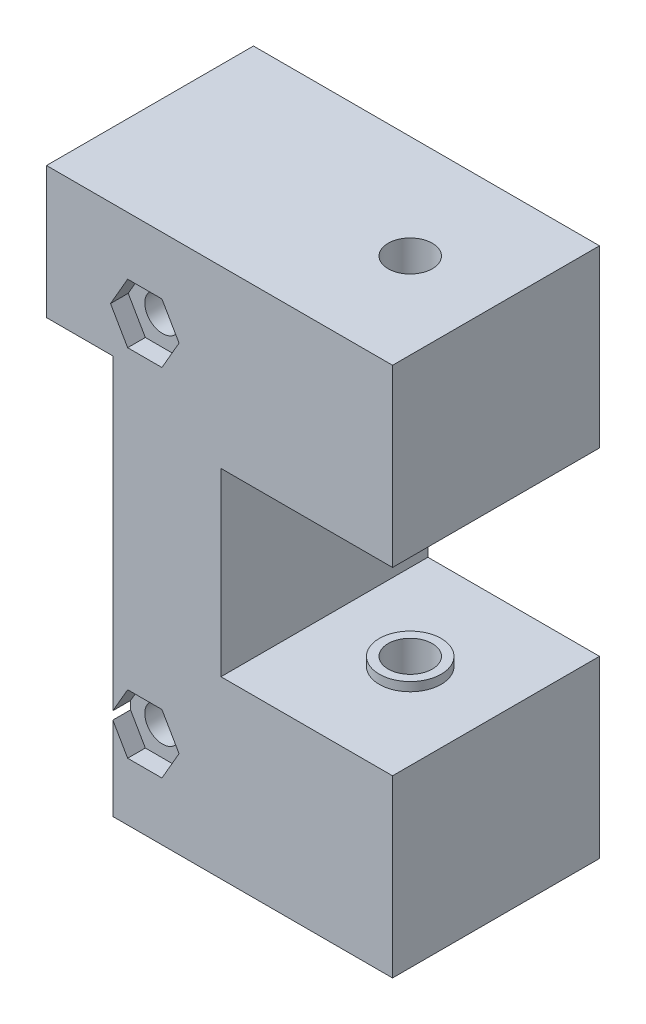
SolidWorks part; units mm, degrees
ref_plane "Front Plane" through (0, 0, 0) normal (0, 0, 1) x (1, 0, 0)
ref_plane "Top Plane" through (0, 0, 0) normal (0, 1, 0) x (1, 0, 0)
ref_plane "Right Plane" through (0, 0, 0) normal (1, 0, 0) x (0, 0, -1)
sketch "MainBlock" plane through (0, 0, 0) normal (0, 0, 1) x (1, 0, 0)
  line L0 (0, 0) -> (39.125, 0)
  line L1 (39.125, 0) -> (39.125, 19.8)
  line L2 (39.125, 19.8) -> (19.725, 19.8)
  line L3 (19.725, 19.8) -> (19.725, 40.2)
  line L4 (19.725, 40.2) -> (39.125, 40.2)
  line L5 (39.125, 40.2) -> (39.125, 60)
  line L6 (39.125, 60) -> (0, 60)
  line L7 (0, 60) -> (0, 0)
  circle A0 centre (11.1125, 50.1) radius 2
  circle A1 centre (11.1125, 9.9) radius 2
  dimension "D4" = 4
  dimension "D1" = 39.125
  dimension "D2" = 60
  dimension "D3" = 20.4
  dimension "D5" = 19.4
  dimension "D6" = 11.1125
  dimension "D7" = 9.9
  dimension "D8" = 9.9
  dimension "D9" = 19.8
  dimension "D10" = 19.8
extrude "MainBlockBoss-Extrude1" add sketch "MainBlock" along normal blind 23.4
sketch "TopHoleCut-Sketch2" plane through (0, 60, 0) normal (0, 1, 0) x (1, 0, 0)
  line L0 (39.125, 0) -> (0, 0) construction
  circle A0 centre (29.425, -11.7) radius 2.5
  dimension "D3" = 5
  dimension "D1" = 11.7
  dimension "D2" = 9.7
extrude "TopHoleCut-Extrude1" cut sketch "TopHoleCut-Sketch2" against normal blind 45
sketch "MountHoleBoreSketch3" plane through (0, 0, 23.4) normal (0, 0, 1) x (1, 0, 0)
  line L1 (14.9875, 50.1) -> (13.05, 53.4558)
  line L2 (13.05, 53.4558) -> (9.175, 53.4558)
  line L3 (9.175, 53.4558) -> (7.2375, 50.1)
  line L4 (7.2375, 50.1) -> (9.175, 46.7442)
  line L5 (9.175, 46.7442) -> (13.05, 46.7442)
  line L6 (13.05, 46.7442) -> (14.9875, 50.1)
  line L7 (14.9875, 9.9) -> (13.05, 13.2558)
  line L8 (13.05, 13.2558) -> (9.175, 13.2558)
  line L9 (9.175, 13.2558) -> (7.2375, 9.9)
  line L10 (7.2375, 9.9) -> (9.175, 6.5442)
  line L11 (9.175, 6.5442) -> (13.05, 6.5442)
  line L12 (13.05, 6.5442) -> (14.9875, 9.9)
  circle A0 centre (11.1125, 50.1) radius 3.3558 construction
  circle A1 centre (11.1125, 9.9) radius 3.3558 construction
  point P10 (11.1125, 53.4558)
  dimension "D1" = 7.75
extrude "MountHoleBoreCut-Extrude2" cut sketch "MountHoleBoreSketch3" against normal blind 2
sketch "TopSpacerSketch4" plane through (0, 40.2, 0) normal (0, -1, 0) x (1, 0, 0)
  circle A0 centre (29.425, 11.7) radius 3.5
  circle A1 centre (29.425, 11.7) radius 2.5
  circle A2 centre (29.425, 11.7) radius 2.5 construction
  dimension "D1" = 7
extrude "TopSpacerBoss-Extrude2" add sketch "TopSpacerSketch4" along normal blind 1
sketch "LowerSpacerSketch5" plane through (0, 19.8, 0) normal (0, 1, 0) x (1, 0, 0)
  circle A0 centre (29.425, -11.7) radius 2.5
  circle A1 centre (29.425, -11.7) radius 2.5 construction
  circle A2 centre (29.425, -11.7) radius 3.5
  circle A3 centre (29.425, -11.7) radius 3.5 construction
extrude "LowerSpacerBoss-Extrude3" add sketch "LowerSpacerSketch5" along normal blind 1
sketch "PushPinHoleSketch1" plane through (0, 0, 0) normal (0, -1, 0) x (1, 0, 0)
  circle A0 centre (29.425, 11.7) radius 1
  circle A1 centre (29.425, 11.7) radius 2.5 construction
  dimension "D1" = 2
extrude "PushPinHoleCut-Extrude1" cut sketch "PushPinHoleSketch1" against normal through all
sketch "MidRailIndentSketch1" plane through (0, 0, 23.4) normal (0, 0, 1) x (1, 0, 0)
  line L0 (0, 60) -> (0, 0) construction
  line L1 (0, 45.1) -> (7.5, 45.1)
  line L2 (0, 45.1) -> (0, 0)
  line L3 (0, 0) -> (7.5, 0)
  line L4 (7.5, 45.1) -> (7.5, 0)
  line L5 (39.125, 60) -> (0, 60) construction
  line L6 (0, 0) -> (39.125, 0) construction
  dimension "D1" = 14.9
  dimension "D3" = 7.5
extrude "MidRailIndentCut-Extrude1" cut sketch "MidRailIndentSketch1" against normal through all
equation "\"BeltTensionerWidth\"= \"MidRailToAlignWithGantryBlock\" + \"BeltTensionerInnerWidth\" / 2 + \"RailThickness\""
equation "\"BeltTensionerHeight\"= 60mm"
equation "\"BeltTensionerDepth\"= \"BeltTensionerBackWallThickness\" + \"BeltTensionerInnerDepth\"'Equals 23.4"
equation "\"BeltTensionerInnerWidth\"= \"20TGT2PulleyDiameter\" + \"BeltTensionerSpaceBetweenPulleyAndWall\""
equation "\"BeltTensionerInnerHeight\"= \"20TGT2PulleyWidth\" * 2 + \"1mmSpacer\" * 3"
equation "\"BeltTensionerBackWallThickness\"= 4mm"
equation "\"BeltTensionerInnerDepth\"= \"20TGT2PulleyDiameter\" + \"BeltTensionerSpaceBetweenPulleyAndWall\""
equation "\"RailThickness\"= .125in'Spec"
equation "\"HoleOffsetFromEdge\"= \"RailThickness\" * 2.5"
equation "\"LinearGBWithRailDepth\"= 12.75mm'Spec"
equation "\"GABDistanceFromBackToFirstPulley\"= 13.5mm"
equation "\"MidRailToAlignWithGantryBlock\"= \"LinearGBWithRailDepth\" + \"GABDistanceFromBackToFirstPulley\"'All outside cogs must align"
equation "\"20TGT2PulleyDiameter\"= 17.9mm'Spec"
equation "\"BeltTensionerSpaceBetweenPulleyAndWall\"= 1.5mm"
equation "\"BeltTensionerMountingHoleDiameter\"= 4.0mm"
equation "\"BeltTensionerMountingHoleOffsetFromTopOrBottom\"= ( \"BeltTensionerHeight\" - \"BeltTensionerInnerHeight\" ) / 4"
equation "\"20TGT2PulleyWidth\"= 8.7mm'The STL of the Pulley in the diagram is a bit larger"
equation "\"1mmSpacer\"= 1mm"
equation "\"SteelShaft5mmHoleDiameter\"= 5mm"
equation "\"BeltTensionerMountingHoleOuterBoreDepth\"= 2mm"
equation "\"BeltTensionerMountingHoleOuterBoreDiameter\"= 7.75mm"
equation "\"7mmx1mmSpacerDiameter\"= 7mm"
equation "\"7mmx1mmSpacerHeight\"= 1mm"
equation "\"D1@MainBlock\" = \"BeltTensionerWidth\""
equation "\"D4@MainBlock\" = \"BeltTensionerMountingHoleDiameter\""
equation "\"D5@MainBlock\" = \"BeltTensionerInnerWidth\""
equation "\"D6@MainBlock\"=\"HoleOffsetFromEdge\" + \"RailThickness\""
equation "\"D7@MainBlock\"=\"BeltTensionerMountingHoleOffsetFromTopOrBottom\""
equation "\"D8@MainBlock\"=\"BeltTensionerMountingHoleOffsetFromTopOrBottom\""
equation "\"D1@MainBlockBoss-Extrude1\" = \"BeltTensionerDepth\""
equation "\"D1@TopHoleCut-Sketch2\" = \"BeltTensionerDepth\" / 2"
equation "\"D3@TopHoleCut-Sketch2\" = \"SteelShaft5mmHoleDiameter\""
equation "\"D1@MountHoleBoreSketch3\" = \"BeltTensionerMountingHoleOuterBoreDiameter\""
equation "\"D1@MountHoleBoreCut-Extrude2\"=\"BeltTensionerMountingHoleOuterBoreDepth\""
equation "\"D1@TopSpacerSketch4\" = \"7mmx1mmSpacerDiameter\""
equation "\"D1@TopSpacerBoss-Extrude2\" = \"7mmx1mmSpacerHeight\""
equation "\"D1@LowerSpacerBoss-Extrude3\" = \"7mmx1mmSpacerHeight\""
equation "\"SteelPinPushHoleDiameter\"= 2mm"
equation "\"D1@PushPinHoleSketch1\" = \"SteelPinPushHoleDiameter\""
equation "\"BeltTensionerSteelShaftHoleDepthFromTop\"= ( \"SteelShaftLength\" - \"BeltTensionerInnerHeight\" ) / 2 + ( \"BeltTensionerHeight\" - \"BeltTensionerInnerHeight\" ) / 2 + \"BeltTensionerInnerHeight\"'Equals 45"
equation "\"SteelShaftLength\"= 30mm"
equation "\"D1@TopHoleCut-Extrude1\"=\"BeltTensionerSteelShaftHoleDepthFromTop\""
equation "\"D2@TopHoleCut-Sketch2\"=\"BeltTensionerWidth\" -\"MidRailToAlignWithGantryBlock\" - \"RailThickness\""
equation "\"D1@MidRailIndentSketch1\"=\"DistanceAboveMidSideRailToBeltTensioner\""
equation "\"LinearRailWidth\"= 12mm'Spec"
equation "\"MidSideRailVerticalOffset\"= \"LinearRailWidth\" + 3mm'Allows space for RodStabilizer to attach to bottom of MidSideRail"
equation "\"DistanceAboveMidSideRailToBeltTensioner\"= \"VS ToTopOfBeltTensionerAlignedWithYAxisGantryBlockUpperPulley\" - \"V8 ToTopOfMidSideRail\"'Equals 14.9"
equation "\"DistanceFromBeltTensionerTopPulleyToBeltTensionerTop\"= \"7mmx1mmSpacerHeight\" + \"BeltTensionerTopHeight\"'Equals 20.8"
equation "\"BeltTensionerTopHeight\"= ( \"BeltTensionerHeight\" - \"BeltTensionerInnerHeight\" ) / 2'Equals 19.8"
equation "\"GABUpperHeight\"= 4mm"
equation "\"D9@MainBlock\"=\"BeltTensionerTopHeight\""
equation "\"D3@MainBlock\"=\"BeltTensionerInnerHeight\""
equation "\"D2@MainBlock\"=\"BeltTensionerHeight\""
equation "\"LegHeight\"= 70mm'Space needed for PSU/Stepper/Electronics"
equation "\"V1 BottomOfLowerRail\"= \"LegHeight\""
equation "\"LowerEnclosureThickness\"= 5mm"
equation "\"StepperShaftLength\"= 24mm'Pulley will be attached to the end"
equation "\"ZAxisLeadScrewLength\"= 200mm"
equation "\"LM8UUHeight\"= 24mm'Spec"
equation "\"V2 ToBedAtTopOfZAxis\"= \"V1 BottomOfLowerRail\" - \"LowerEnclosureThickness\" + \"StepperShaftLength\" + \"ZAxisLeadScrewLength\" - \"LM8UUHeight\" / 2'Equals 277"
equation "\"BedToBuildPlateStandoffLength\"= 15mm"
equation "\"BuildPlateHeight\"= 8mm'Spec"
equation "\"V4 ToTopOfBuildPlate/HotEndTip\"= \"V2 ToBedAtTopOfZAxis\" + \"BedToBuildPlateStandoffLength\" + \"BuildPlateHeight\""
equation "\"HotEndToTopOfXAxisGB\"= 71.68487mm'Equals 71.68487. Measured after installed onto X-Axis linear rail guide block"
equation "\"LinearGBWidth\"= 27mm'Spec"
equation "\"TopOfGBToBottomOfLinearRail\"= \"LinearGBWidth\" / 2 + \"LinearRailWidth\" / 2'Equals 19.5"
equation "\"V5 ToBottomOfXAxisLinearRail\"= \"V4 ToTopOfBuildPlate/HotEndTip\" + \"HotEndToTopOfXAxisGB\" - \"TopOfGBToBottomOfLinearRail\"'Equals 352.18487"
equation "\"GABMidWallHeight\"= 28mm'Must equal 28 or changes alignment"
equation "\"GABLowerHeight\"= 4mm"
equation "\"GABHeight\"= \"GABLowerHeight\" + \"GABMidWallHeight\" + \"GABUpperHeight\""
equation "\"V6 ToMiddleOfYAxisGantryBlock\"= \"V5 ToBottomOfXAxisLinearRail\" - \"GABHeight\" / 2'Equals 334.18487"
equation "\"V8 ToTopOfMidSideRail\"= \"V6 ToMiddleOfYAxisGantryBlock\" + \"MidSideRailVerticalOffset\"'Equals 349.18487"
equation "\"VS ToTopOfBeltTensionerAlignedWithYAxisGantryBlockUpperPulley\"= \"V5 ToBottomOfXAxisLinearRail\" - \"DistanceFromXAxisLinearRailBottomAndTopOfGantryPulley\" + \"DistanceFromBeltTensionerTopPulleyToBeltTensionerTop\"'Equals 364.08487"
equation "\"DistanceFromXAxisLinearRailBottomAndTopOfGantryPulley\"= \"GABUpperHeight\" + \"GABMidShortRiserHeight\" - \"GABRiserBossOffset\"'Equals 8.9"
equation "\"GABMidShortRiserHeight\"= \"GABMidWallHeight\" / 2 - \"20TGT2PulleyWidth\"'Equals 5.3"
equation "\"GABRiserBossOffset\"= 0.4mm'Aligns Pulleys inside edges to be 2.5mm (.5mm apart top to bottom)"
